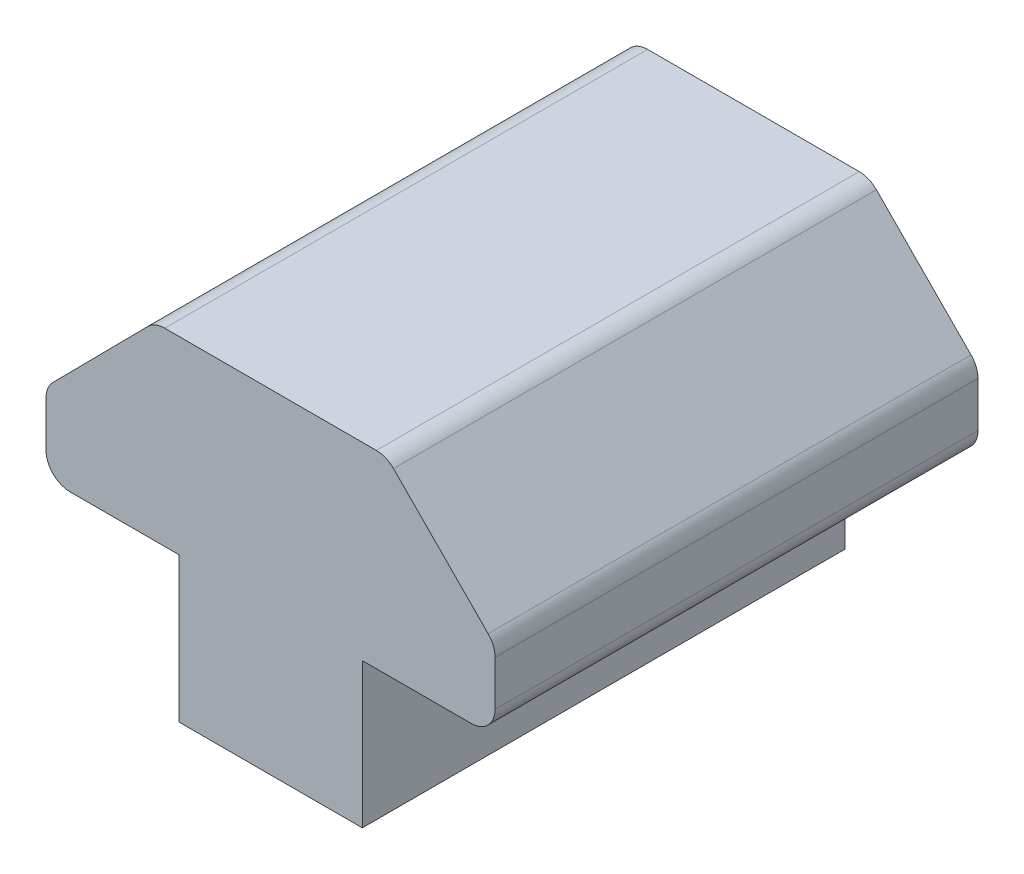
SolidWorks part; units mm, degrees
ref_plane "Front Plane" through (0, 0, 0) normal (0, 0, 1) x (1, 0, 0)
ref_plane "Top Plane" through (0, 0, 0) normal (0, 1, 0) x (1, 0, 0)
ref_plane "Right Plane" through (0, 0, 0) normal (1, 0, 0) x (0, 0, -1)
sketch "Sketch1" plane through (0, 0, 0) normal (0, 0, 1) x (1, 0, 0)
  line L0 (0, 0) -> (0, 44.9793) construction
  line L5 (3.8, 0) -> (-3.8, 0)
  line L6 (-3.8, 0) -> (-3.8, 6)
  line L7 (-3.8, 6) -> (-9.3, 6)
  line L8 (-9.3, 6) -> (-9.3, 9.28)
  line L9 (-9.3, 9.28) -> (-4.8, 13.8308)
  line L10 (-4.8, 13.8308) -> (4.8, 13.8308)
  line L11 (0, 13.8308) -> (0, 0) construction
  line L12 (9.3, 9.28) -> (4.8, 13.8308)
  line L13 (9.3, 6) -> (9.3, 9.28)
  line L14 (3.8, 6) -> (9.3, 6)
  line L15 (3.8, 0) -> (3.8, 6)
  dimension "D1" = 3.8
  dimension "D2" = 6
  dimension "D3" = 5.5
  dimension "D4" = 3.28
  dimension "D5" = 6.4
  dimension "D6" = 4.8
extrude "Boss-Extrude1" add sketch "Sketch1" along normal blind 20
fillet "Fillet1" radius 1 6 edges at (9.3, 6, 10) (-9.3, 6, 10) (-9.3, 9.28, 10) (9.3, 9.28, 10) (-4.8, 13.8308, 10) (4.8, 13.8308, 10)
